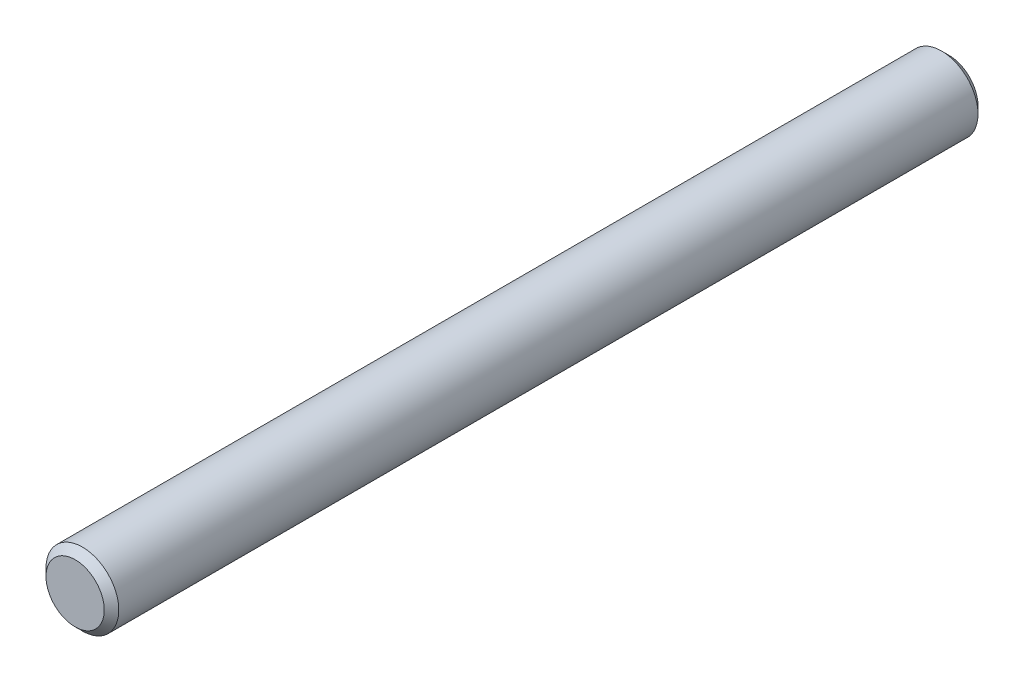
SolidWorks part; units mm, degrees
material "Plain Carbon Steel"
ref_plane "Front" through (0, 0, 0) normal (0, 0, 1) x (1, 0, 0)
ref_plane "Top" through (0, 0, 0) normal (0, 1, 0) x (1, 0, 0)
ref_plane "Right" through (0, 0, 0) normal (1, 0, 0) x (0, 0, -1)
sketch "Sketch1" plane through (0, 0, 0) normal (0, 0, 1) x (1, 0, 0)
  circle A0 centre (0, 0) radius 12.7
  dimension "dia" = 25.4
extrude "Extrude1" add sketch "Sketch1" along normal mid plane 304.8
sketch "Sketch2" plane through (0, 0, 0) normal (1, 0, 0) x (0, 0, -1)
  line L0 (152.4, 12.7) -> (148.59, 12.7) construction
  line L1 (152.4, 12.7) -> (-152.4, 12.7) construction
  line L2 (148.59, 12.7) -> (117.6337, 12.7) construction
  line L3 (117.6337, 12.7) -> (110.49, 12.7) construction
  line L4 (110.49, 12.7) -> (101.6, 12.7) construction
  line L5 (101.6, 12.7) -> (98.9432, 12.7) construction
  line L7 (90.0532, 12.7) -> (83.7032, 12.7) construction
  line L8 (83.7032, 12.7) -> (74.8132, 12.7) construction
  line L10 (-152.4, -12.7) -> (152.4, -12.7) construction
  line L11 (-152.4, 12.7) -> (-149.86, 12.7) construction
  line L12 (-149.86, 12.7) -> (-149.86, -12.7) construction
  line L13 (98.9432, 12.7) -> (90.0532, 12.7) construction
  line L14 (90.0532, 12.7) -> (90.0532, -12.7) construction
  line L15 (110.49, 12.7) -> (110.49, -12.7) construction
  line L16 (74.8132, 12.7) -> (68.4632, 12.7) construction
  line L17 (68.4632, 12.7) -> (59.5732, 12.7) construction
  line L18 (59.5732, 12.7) -> (53.2232, 12.7) construction
  line L19 (53.2232, 12.7) -> (44.3332, 12.7) construction
  line L20 (74.8132, 12.7) -> (74.8132, -12.7) construction
  line L21 (59.5732, 12.7) -> (59.5732, -12.7) construction
  line L22 (44.3332, 12.7) -> (44.3332, -12.7) construction
  line L23 (44.3332, 12.7) -> (37.9832, 12.7) construction
  line L24 (37.9832, 12.7) -> (29.0932, 12.7) construction
  line L25 (29.0932, 12.7) -> (29.0932, -12.7) construction
  line L26 (29.0932, 12.7) -> (22.7432, 12.7) construction
  line L27 (22.7432, 12.7) -> (13.8532, 12.7) construction
  line L28 (13.8532, 12.7) -> (7.5032, 12.7) construction
  line L29 (7.5032, 12.7) -> (-1.3868, 12.7) construction
  line L30 (13.8532, 12.7) -> (13.8532, -12.7) construction
  line L31 (-1.3868, 12.7) -> (-1.3868, -12.7) construction
  line L32 (-1.3868, 12.7) -> (-7.7368, 12.7) construction
  line L33 (-7.7368, 12.7) -> (-16.6268, 12.7) construction
  line L34 (-16.6268, 12.7) -> (-19.2837, 12.7) construction
  line L35 (-19.2837, 12.7) -> (-28.1737, 12.7) construction
  line L36 (-28.1737, 12.7) -> (-28.1737, -12.7) construction
  line L37 (-28.1737, 12.7) -> (-117.0737, 12.7) construction
  line L38 (-117.0737, 12.7) -> (-117.0737, -12.7) construction
  line L39 (101.6, 12.7) -> (101.6, -12.7) construction
  point P0 (-152.4, 12.7)
  point P1 (152.4, 12.7)
  dimension "D1" = 3.81
  dimension "D2" = 30.9562
  dimension "D3" = 7.1437
  dimension "D4" = 8.89
  dimension "D5" = 2.6568
  dimension "D6" = 8.89
  dimension "D7" = 8.89
  dimension "D8" = 2.54
  dimension "D9" = 6.35
  dimension "D10" = 6.35
  dimension "D11" = 8.89
  dimension "D12" = 6.35
  dimension "D13" = 8.89
  dimension "D14" = 6.35
  dimension "D15" = 8.89
  dimension "D16" = 6.35
  dimension "D17" = 8.89
  dimension "D18" = 6.35
  dimension "D19" = 8.89
  dimension "D20" = 6.35
  dimension "D21" = 8.89
  dimension "D22" = 2.6568
  dimension "D23" = 8.89
  dimension "D24" = 88.9
chamfer "Chamfer1" distance 2.54 angle 45 2 edges at (12.7, 0, -152.4) (12.7, 0, 152.4)
equation "\"D1@Chamfer1\" = \"dia@Sketch1\" * .1"
